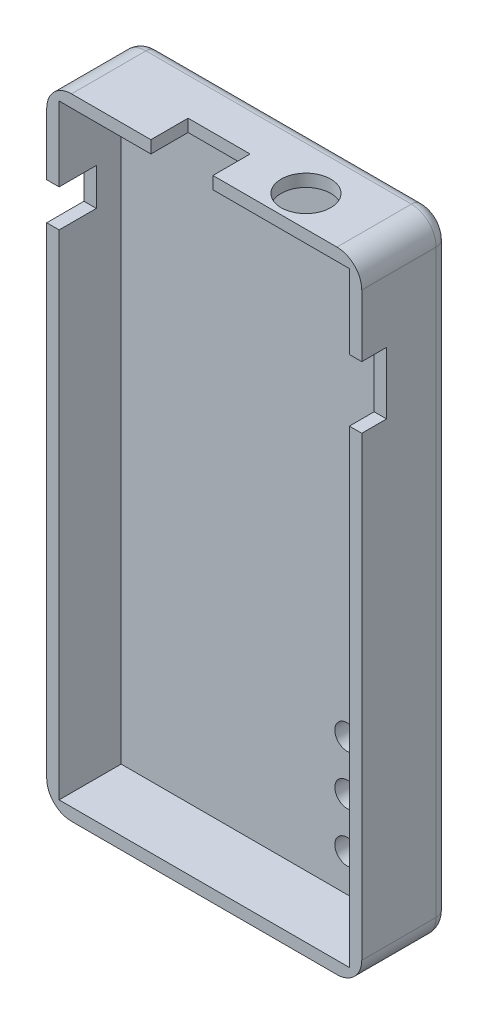
SolidWorks part; units mm, degrees
ref_plane "Front Plane" through (0, 0, 0) normal (0, 0, 1) x (1, 0, 0)
ref_plane "Top Plane" through (0, 0, 0) normal (0, 1, 0) x (1, 0, 0)
ref_plane "Right Plane" through (0, 0, 0) normal (1, 0, 0) x (0, 0, -1)
sketch "Sketch1" plane through (0, 0, 0) normal (0, 0, 1) x (1, 0, 0)
  line L1 (0, 0) -> (25.4, 0)
  line L2 (0, 0) -> (0, 50.8)
  line L3 (0, 50.8) -> (25.4, 50.8)
  line L4 (25.4, 0) -> (25.4, 50.8)
  dimension "D1" = 25.4
  dimension "D2" = 50.8
extrude "Boss-Extrude1" add sketch "Sketch1" along normal blind 2
sketch "Sketch2" plane through (0, 0, 2) normal (0, 0, 1) x (1, 0, 0)
  line L0 (25.4, 50.8) -> (0, 50.8) construction
  line L1 (24.4, 49.8) -> (1, 49.8)
  line L2 (24.4, 49.8) -> (24.4, 1)
  line L3 (24.4, 1) -> (1, 1)
  line L4 (1, 49.8) -> (1, 1)
  line L5 (25.4, 0) -> (25.4, 50.8) construction
  line L6 (0, -1.1) -> (0, 1.1) construction
  line L7 (1.1, 0) -> (-1.1, 0) construction
  line L8 (25.4, 50.8) -> (0, 50.8) construction
  line L9 (0, 50.8) -> (0, 0) construction
  line L10 (0, 0) -> (25.4, 0) construction
  line L11 (25.4, 0) -> (25.4, 50.8) construction
  line L12 (25.4, 50.8) -> (0, 50.8)
  line L13 (0, 50.8) -> (0, 0)
  line L14 (0, 0) -> (25.4, 0)
  line L15 (25.4, 0) -> (25.4, 50.8)
  dimension "D1" = 1
  dimension "D2" = 1
  dimension "D3" = 1
  dimension "D4" = 1
extrude "Boss-Extrude2" add sketch "Sketch2" along normal blind 5
fillet "Fillet1" radius 2 4 edges at (0, 0, 3.5) (25.4, 0, 3.5) (0, 50.8, 3.5) (25.4, 50.8, 3.5)
fillet "Fillet2" radius 1 8 edges at (24.8142, 0.5858, 0) (12.7, 0, 0) (0.5858, 0.5858, 0) (0, 25.4, 0) (0.5858, 50.2142, 0) (12.7, 50.8, 0) (24.8142, 50.2142, 0) (25.4, 25.4, 0)
sketch "Sketch4" plane through (25.4, 0, 0) normal (1, 0, 0) x (0, 0, -1)
  line L0 (-7, 2) -> (-7, 48.8) construction
  line L1 (-7, 43.8) -> (-5, 43.8)
  line L2 (-7, 43.8) -> (-7, 38.8)
  line L3 (-7, 38.8) -> (-5, 38.8)
  line L4 (-5, 43.8) -> (-5, 38.8)
  line L6 (-1, 48.8) -> (-7, 48.8) construction
  dimension "D1" = 5
  dimension "D2" = 5
  dimension "D3" = 2
extrude "Cut-Extrude1" cut sketch "Sketch4" against normal up to next
sketch "Sketch6" plane through (0, 50.8, 0) normal (0, 1, 0) x (1, 0, 0)
  line L0 (23.4, -7) -> (23.4, -1) construction
  line L1 (23.4, -7) -> (2, -7) construction
  circle A0 centre (18.4, -4.5) radius 2
  dimension "D2" = 4
  dimension "D1" = 5
  dimension "D3" = 2.5
extrude "Cut-Extrude3" cut sketch "Sketch6" against normal up to next
sketch "Sketch7" plane through (0, 50.8, 0) normal (0, 1, 0) x (1, 0, 0)
  line L0 (23.4, -7) -> (2, -7) construction
  line L1 (8.4, -7) -> (13.4, -7)
  line L2 (8.4, -7) -> (8.4, -4)
  line L3 (8.4, -4) -> (13.4, -4)
  line L4 (13.4, -7) -> (13.4, -4)
  line L5 (23.4, -7) -> (23.4, -1) construction
  dimension "D1" = 10
  dimension "D2" = 5
  dimension "D3" = 3
extrude "Cut-Extrude4" cut sketch "Sketch7" against normal up to next
sketch "Sketch8" plane through (0, 0, 0) normal (-1, 0, 0) x (0, 0, 1)
  line L0 (7, 48.8) -> (7, 2) construction
  line L1 (7, 43.8) -> (4, 43.8)
  line L2 (7, 43.8) -> (7, 40.8)
  line L3 (7, 40.8) -> (4, 40.8)
  line L4 (4, 43.8) -> (4, 40.8)
  line L5 (7, 48.8) -> (1, 48.8) construction
  dimension "D1" = 5
  dimension "D2" = 3
  dimension "D3" = 3
extrude "Cut-Extrude5" cut sketch "Sketch8" against normal up to next
sketch "Sketch9" plane through (0, 0, 0) normal (0, 0, -1) x (-1, 0, 0)
  line L0 (-23.4, 1) -> (-2, 1) construction
  circle A0 centre (-19.2297, 4) radius 1
  circle A1 centre (-19.2297, 8) radius 1
  circle A2 centre (-19.2297, 12) radius 1
  dimension "D2" = 2
  dimension "D5" = 2
  dimension "D6" = 2
  dimension "D1" = 3
  dimension "D3" = 4
  dimension "D4" = 4
extrude "Cut-Extrude6" cut sketch "Sketch9" against normal up to next
equation "\"width\"=1"
equation "\"D1@Sketch1\"=\"width\""
equation "\"length\"=2"
equation "\"D2@Sketch1\"=\"length\""
equation "\"lip_thickness\"=0.0393701"
equation "\"D1@Sketch2\"=\"lip_thickness\""
equation "\"D2@Sketch2\"=\"lip_thickness\""
equation "\"D3@Sketch2\"=\"lip_thickness\""
equation "\"D4@Sketch2\"=\"lip_thickness\""
equation "\"container_thickness\"=0.0787402"
equation "\"D1@Boss-Extrude1\"=\"container_thickness\""
equation "\"lip_height\"= 5mm"
equation "\"D1@Boss-Extrude2\"=\"lip_height\""
equation "\"side_fillet\"= 2mm"
equation "\"D1@Fillet1\"=\"side_fillet\""
equation "\"face_fillet\"= 1mm"
equation "\"D1@Fillet2\"=\"face_fillet\""
equation "\"switch_offset\"=0.19685"
equation "\"D1@Sketch4\"=\"switch_offset\""
equation "\"switch_length\"=0.19685"
equation "\"D2@Sketch4\"=\"switch_length\""
equation "\"switch_height\"=0.0787402"
equation "\"D3@Sketch4\"=\"switch_height\""
equation "\"jack_offset\"=0.19685"
equation "\"D1@Sketch6\"=\"jack_offset\""
equation "\"jack_diameter\"=0.15748"
equation "\"D2@Sketch6\"=\"jack_diameter\""
equation "\"jack_offset2\"=0.0984252"
equation "\"D3@Sketch6\"=\"jack_offset2\""
equation "\"charger_offset\"=0.393701"
equation "\"D1@Sketch7\"=\"charger_offset\""
equation "\"charget_width\"=0.19685"
equation "\"D2@Sketch7\"=\"charget_width\""
equation "\"charger_height\"=0.11811"
equation "\"D3@Sketch7\"=\"charger_height\""
equation "\"button_offset\"=0.19685"
equation "\"D1@Sketch8\"=\"button_offset\""
equation "\"button_width\"=0.11811"
equation "\"D2@Sketch8\"=\"button_width\""
equation "\"button_height\"=0.11811"
equation "\"D3@Sketch8\"=\"button_height\""
equation "\"led_offset\"=0.11811"
equation "\"D1@Sketch9\"=\"led_offset\""
equation "\"led_diameter\"=0.0787402"
equation "\"D2@Sketch9\"=\"led_diameter\""
equation "\"led_spacing\"=0.15748"
equation "\"D3@Sketch9\"=\"led_spacing\""
equation "\"D4@Sketch9\"=\"led_spacing\""
equation "\"D5@Sketch9\"=\"led_diameter\""
equation "\"D6@Sketch9\"=\"led_diameter\""
